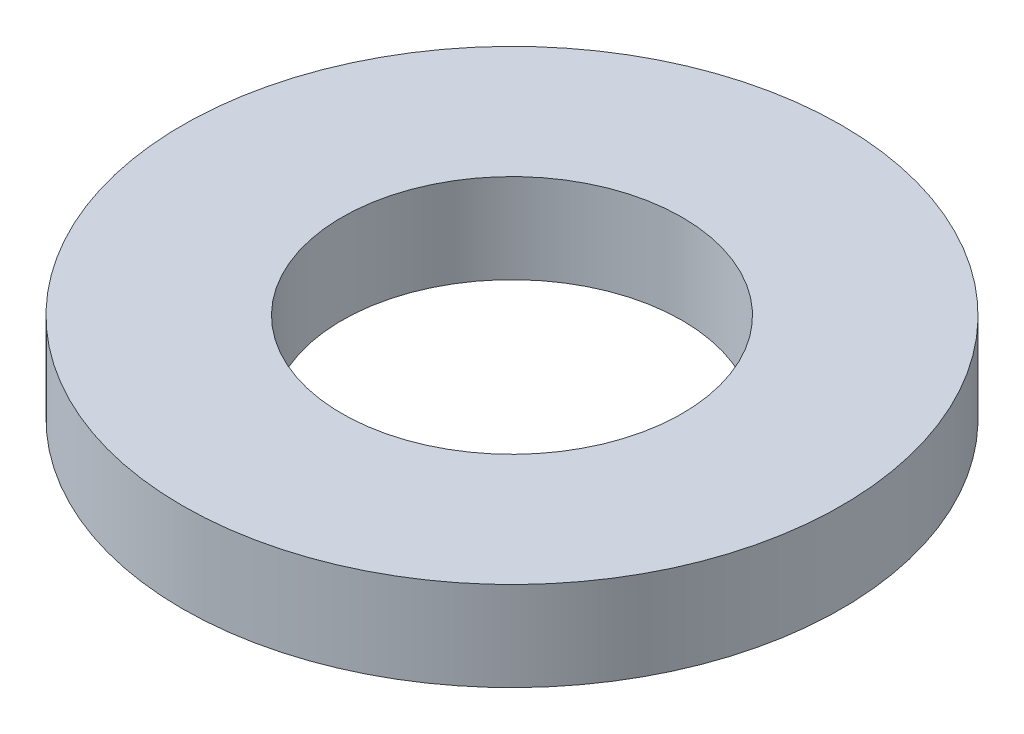
SolidWorks part; units mm, degrees
ref_plane "Front Plane" through (0, 0, 0) normal (0, 0, 1) x (1, 0, 0)
ref_plane "Top Plane" through (0, 0, 0) normal (0, 1, 0) x (1, 0, 0)
ref_plane "Right Plane" through (0, 0, 0) normal (1, 0, 0) x (0, 0, -1)
sketch "Sketch1" plane through (0, 0, 0) normal (0, 1, 0) x (1, 0, 0)
  circle A0 centre (0, 0) radius 77.5
  dimension "FLANGE_OD" = 155
extrude "Boss-Extrude1" add sketch "Sketch1" along normal blind 21
sketch "Sketch2" plane through (0, 0, 0) normal (0, 1, 0) x (1, 0, 0)
  circle A0 centre (0, 0) radius 40
  dimension "BORE_D" = 80
extrude "Cut-Extrude1" cut sketch "Sketch2" along normal through all
sketch "Sketch3" plane through (0, 21, 0) normal (0, 1, 0) x (1, 0, 0)
  circle A0 centre (0, 0) radius 34.0947 construction
  circle A1 centre (-34.0947, 0) radius 5.4036
  dimension "BOLT_D" = 10.8072
  dimension "BOLT_PCD" = 68.1895
extrude "Cut-Extrude2" cut sketch "Sketch3" against normal blind 19.0438 rebuild error yes
pattern_circular "CirPattern1" count 3 over 360 rebuild error yes
